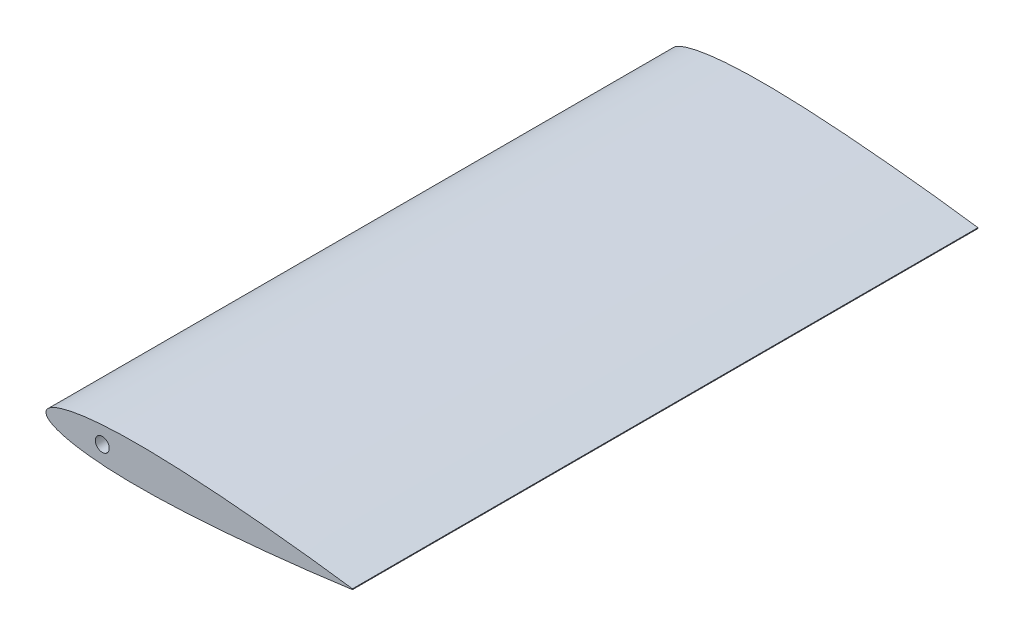
SolidWorks part; units mm, degrees
material "ABS"
ref_plane "Front Plane" through (0, 0, 0) normal (0, 0, 1) x (1, 0, 0)
ref_plane "Top Plane" through (0, 0, 0) normal (0, 1, 0) x (1, 0, 0)
ref_plane "Right Plane" through (0, 0, 0) normal (1, 0, 0) x (0, 0, -1)
curve "Curve1"
  spline degree 3 poles (1, 0.0013, 0) (0.9998, 0.0013, 0) (0.999, 0.0014, 0) (0.9973, 0.0016, 0) (0.9944, 0.002, 0) (0.9903, 0.0026, 0) (0.9851, 0.0033, 0) (0.9788, 0.0042, 0) (0.9713, 0.0052, 0) (0.9627, 0.0064, 0) (0.9531, 0.0077, 0) (0.9424, 0.0091, 0) (0.9307, 0.0106, 0) (0.9179, 0.0122, 0) (0.9042, 0.014, 0) (0.8895, 0.0158, 0) (0.874, 0.0177, 0) (0.8575, 0.0196, 0) (0.8402, 0.0217, 0) (0.8222, 0.0237, 0) (0.8033, 0.0259, 0) (0.7838, 0.028, 0) (0.7636, 0.0302, 0) (0.7428, 0.0324, 0) (0.7214, 0.0345, 0) (0.6995, 0.0367, 0) (0.6772, 0.0388, 0) (0.6544, 0.0409, 0) (0.6313, 0.043, 0) (0.6078, 0.045, 0) (0.5841, 0.0469, 0) (0.5602, 0.0488, 0) (0.5362, 0.0505, 0) (0.5121, 0.0522, 0) (0.4879, 0.0537, 0) (0.4638, 0.0551, 0) (0.4398, 0.0563, 0) (0.4159, 0.0574, 0) (0.3922, 0.0583, 0) (0.3688, 0.0591, 0) (0.3456, 0.0596, 0) (0.3228, 0.0599, 0) (0.3005, 0.0601, 0) (0.2786, 0.06, 0) (0.2572, 0.0596, 0) (0.2364, 0.0591, 0) (0.2162, 0.0583, 0) (0.1966, 0.0572, 0) (0.1778, 0.056, 0) (0.1597, 0.0544, 0) (0.1425, 0.0527, 0) (0.126, 0.0507, 0) (0.1104, 0.0486, 0) (0.0958, 0.0462, 0) (0.0821, 0.0436, 0) (0.0693, 0.0408, 0) (0.0576, 0.0378, 0) (0.0468, 0.0347, 0) (0.0372, 0.0313, 0) (0.0286, 0.0279, 0) (0.0211, 0.0243, 0) (0.0147, 0.0206, 0) (0.0094, 0.0167, 0) (0.0053, 0.0128, 0) (0.0023, 0.0087, 0) (0.0004, 0.0044, 0) (-0.0002, 0, 0) (0.0004, -0.0044, 0) (0.0023, -0.0087, 0) (0.0053, -0.0128, 0) (0.0094, -0.0167, 0) (0.0147, -0.0206, 0) (0.0211, -0.0243, 0) (0.0286, -0.0279, 0) (0.0372, -0.0313, 0) (0.0468, -0.0347, 0) (0.0576, -0.0378, 0) (0.0693, -0.0408, 0) (0.0821, -0.0436, 0) (0.0958, -0.0462, 0) (0.1104, -0.0486, 0) (0.126, -0.0507, 0) (0.1425, -0.0527, 0) (0.1597, -0.0544, 0) (0.1778, -0.056, 0) (0.1966, -0.0572, 0) (0.2162, -0.0583, 0) (0.2364, -0.0591, 0) (0.2572, -0.0596, 0) (0.2786, -0.06, 0) (0.3005, -0.0601, 0) (0.3228, -0.0599, 0) (0.3456, -0.0596, 0) (0.3688, -0.0591, 0) (0.3922, -0.0583, 0) (0.4159, -0.0574, 0) (0.4398, -0.0563, 0) (0.4638, -0.0551, 0) (0.4879, -0.0537, 0) (0.5121, -0.0522, 0) (0.5362, -0.0505, 0) (0.5602, -0.0488, 0) (0.5841, -0.0469, 0) (0.6078, -0.045, 0) (0.6313, -0.043, 0) (0.6544, -0.0409, 0) (0.6772, -0.0388, 0) (0.6995, -0.0367, 0) (0.7214, -0.0345, 0) (0.7428, -0.0324, 0) (0.7636, -0.0302, 0) (0.7838, -0.028, 0) (0.8033, -0.0259, 0) (0.8222, -0.0237, 0) (0.8402, -0.0217, 0) (0.8575, -0.0196, 0) (0.874, -0.0177, 0) (0.8895, -0.0158, 0) (0.9042, -0.014, 0) (0.9179, -0.0122, 0) (0.9307, -0.0106, 0) (0.9424, -0.0091, 0) (0.9531, -0.0077, 0) (0.9627, -0.0064, 0) (0.9713, -0.0052, 0) (0.9788, -0.0042, 0) (0.9851, -0.0033, 0) (0.9903, -0.0026, 0) (0.9944, -0.002, 0) (0.9973, -0.0016, 0) (0.999, -0.0014, 0) (0.9998, -0.0013, 0) (1, -0.0013, 0) knots 0 0 0 0 0.000289 0.001156 0.002598 0.004612 0.007194 0.010336 0.014031 0.018272 0.023046 0.028343 0.03415 0.040454 0.047238 0.054489 0.062187 0.070314 0.078852 0.08778 0.097078 0.106722 0.116691 0.126961 0.137507 0.148306 0.159331 0.170556 0.181957 0.193504 0.205171 0.216932 0.228758 0.240621 0.252495 0.26435 0.276161 0.287898 0.299536 0.311047 0.322405 0.333584 0.344559 0.355306 0.3658 0.376018 0.385937 0.395538 0.404798 0.413699 0.422221 0.430349 0.438066 0.445357 0.452209 0.458612 0.464554 0.47003 0.475035 0.479569 0.483637 0.48725 0.490431 0.493219 0.495674 0.497891 0.5 0.502109 0.504326 0.506781 0.509569 0.51275 0.516363 0.520431 0.524965 0.52997 0.535446 0.541388 0.547791 0.554643 0.561934 0.569651 0.577779 0.586301 0.595202 0.604462 0.614063 0.623982 0.6342 0.644694 0.655441 0.666416 0.677595 0.688953 0.700464 0.712102 0.723839 0.73565 0.747505 0.759379 0.771242 0.783068 0.794829 0.806496 0.818043 0.829444 0.840669 0.851694 0.862493 0.873039 0.883309 0.893278 0.902922 0.91222 0.921148 0.929686 0.937813 0.945511 0.952762 0.959546 0.96585 0.971657 0.976954 0.981728 0.985969 0.989664 0.992806 0.995388 0.997402 0.998844 0.999711 1 1 1 1
sketch "Sketch7" plane through (0, 0, 0) normal (0, 0, 1) x (1, 0, 0)
  line L0 (1, -0.1046) -> (1, 0.0066)
  spline S1 degree 3 poles (1, 0.0066) (0.1587, 0.1247) (-3.0116, 0.5533) (-7.4263, 1.0787) (-12.699, 1.6223) (-16.697, 1.9793) (-20.5193, 2.2595) (-23.6878, 2.4437) (-26.8012, 2.5658) (-29.7944, 2.6122) (-32.3272, 2.5764) (-34.3977, 2.4825) (-36.0221, 2.3618) (-37.507, 2.2006) (-38.649, 2.0297) (-39.4815, 1.872) (-40.0437, 1.7489) (-40.5616, 1.6177) (-41.0342, 1.4791) (-41.4602, 1.3334) (-41.8389, 1.1813) (-42.1694, 1.023) (-42.4512, 0.859) (-42.684, 0.6896) (-42.8671, 0.5144) (-43.0004, 0.333) (-43.0818, 0.1444) (-43.1089, -0.049) (-43.0818, -0.2425) (-43.0004, -0.431) (-42.8671, -0.6124) (-42.684, -0.7876) (-42.4512, -0.9571) (-42.1694, -1.121) (-41.8389, -1.2793) (-41.4602, -1.4315) (-41.0342, -1.5771) (-40.5616, -1.7158) (-40.0437, -1.8469) (-39.268, -2.0168) (-38.1929, -2.2036) (-36.7829, -2.3841) (-34.9303, -2.5522) (-32.6047, -2.6704) (-29.4493, -2.7151) (-26.1022, -2.6459) (-22.6345, -2.4865) (-19.4624, -2.2849) (-15.9943, -2.0156) (-12.9553, -1.7393) (-9.0386, -1.3466) (-5.1647, -0.9134) (-1.4665, -0.4436) (0.3805, -0.1913) (0.9229, -0.1154) (1, -0.1046) knots 0 0 0 0 0.028343 0.106722 0.148306 0.205171 0.240621 0.276161 0.311047 0.344559 0.376018 0.395538 0.413699 0.430349 0.445357 0.452209 0.458612 0.464554 0.47003 0.475035 0.479569 0.483637 0.48725 0.490431 0.493219 0.495674 0.497891 0.5 0.502109 0.504326 0.506781 0.509569 0.51275 0.516363 0.520431 0.524965 0.52997 0.535446 0.541388 0.547791 0.561934 0.577779 0.595202 0.623982 0.655441 0.700464 0.73565 0.771242 0.806496 0.851694 0.873039 0.937813 0.981728 0.997402 1 1 1 1
extrude "Boss-Extrude4" add sketch "Sketch7" along normal blind 90
sketch "Sketch8" plane through (0, 0, 90) normal (0, 0, 1) x (1, 0, 0)
  line L0 (1, -0.1046) -> (1, 0.0066) construction
  circle A0 centre (-35, 0) radius 1
  dimension "D1" = 36
extrude "Cut-Extrude3" cut sketch "Sketch8" against normal through all
